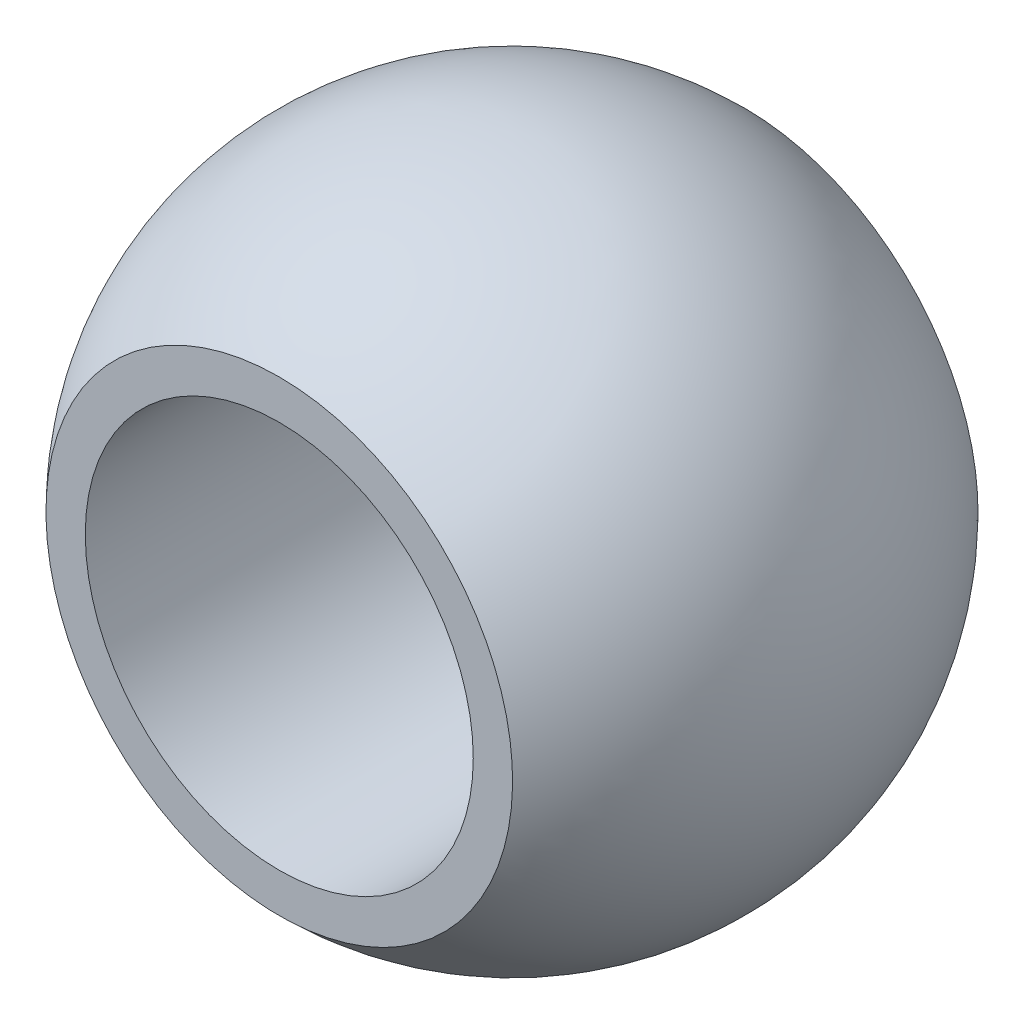
SolidWorks part; units mm, degrees
material "Plain Carbon Steel"
ref_plane "Front Plane" through (0, 0, 0) normal (0, 0, 1) x (1, 0, 0)
ref_plane "Top Plane" through (0, 0, 0) normal (0, 1, 0) x (1, 0, 0)
ref_plane "Right Plane" through (0, 0, 0) normal (1, 0, 0) x (0, 0, -1)
sketch "Sketch1" plane through (0, 0, 0) normal (1, 0, 0) x (0, 0, -1)
  line L0 (9.8914, 0) -> (-12.0666, 0) construction
  line L1 (9.525, 7.94) -> (-9.525, 7.94)
  line L2 (-9.525, 7.94) -> (-9.525, 9.549)
  line L3 (9.525, 7.94) -> (9.525, 9.549)
  arc A0 (9.525, 9.549) -> (-9.525, 9.549) centre (0, 0) ccw
  point P3 (0, 7.94)
  dimension "D1" = 7.94
  dimension "D3" = 13.4874
  dimension "D2" = 19.05
revolve "Revolve1" add sketch "Sketch1"
sketch "Sketch2" plane through (0, 0, 0) normal (1, 0, 0) x (0, 0, -1)
  line L0 (0, 16.302) -> (0, -16.302) construction
  line L1 (-11.2912, 0) -> (11.2912, 0) construction
  point P5 (0, 0)
